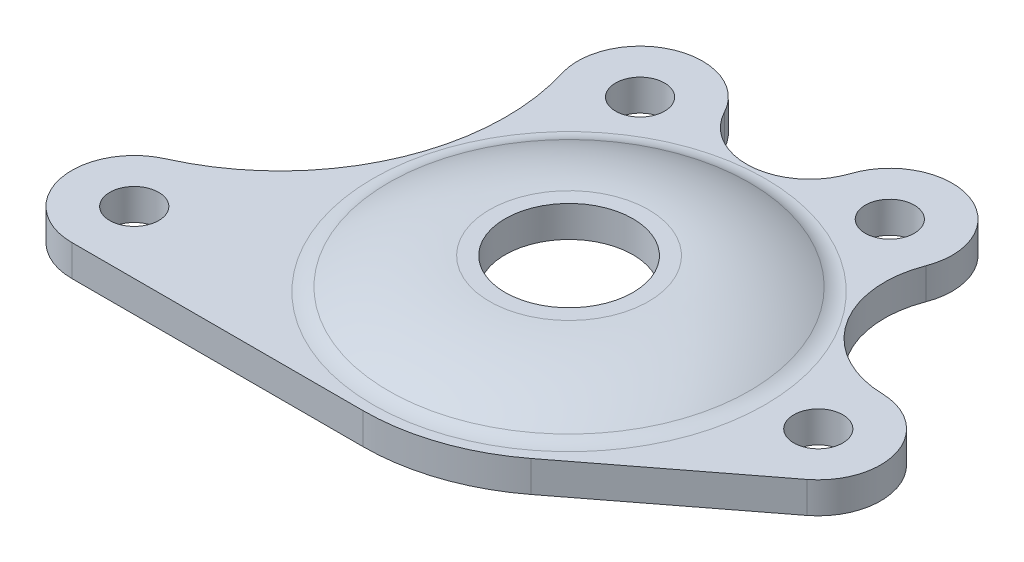
SolidWorks part; units mm, degrees
material "Alum Plate"
ref_plane "Front Plane" through (0, 0, 0) normal (0, 0, 1) x (1, 0, 0)
ref_plane "Top Plane" through (0, 0, 0) normal (0, 1, 0) x (1, 0, 0)
ref_plane "Right Plane" through (0, 0, 0) normal (1, 0, 0) x (0, 0, -1)
sketch "Top Layout" plane through (0, 0, 0) normal (0, 1, 0) x (1, 0, 0)
  line L0 (-114.046, -123.825) -> (-104.775, -123.825) construction
  line L1 (-104.775, -142.875) -> (-101.6, -142.875)
  line L2 (-104.775, -142.875) -> (-104.775, -104.775)
  line L3 (-104.775, -104.775) -> (-101.6, -104.775)
  line L4 (-101.6, -142.875) -> (-101.6, -104.775)
  line L5 (-104.775, -142.875) -> (-101.6, -104.775) construction
  line L6 (-104.775, -104.775) -> (-101.6, -142.875) construction
  line L7 (-19.05, -105.8164) -> (-101.6, -105.8164)
  line L8 (-19.05, -105.8164) -> (-19.05, -141.8336)
  line L9 (-19.05, -141.8336) -> (-101.6, -141.8336)
  line L10 (-101.6, -105.8164) -> (-101.6, -141.8336)
  line L11 (-19.05, -105.8164) -> (-101.6, -141.8336) construction
  line L12 (-19.05, -141.8336) -> (-101.6, -105.8164) construction
  line L13 (-133.096, -85.725) -> (-114.046, -85.725)
  line L14 (-133.096, -85.725) -> (-133.096, -161.925)
  line L15 (-133.096, -161.925) -> (-114.046, -161.925)
  line L16 (-114.046, -85.725) -> (-114.046, -161.925)
  line L17 (-133.096, -85.725) -> (-114.046, -161.925) construction
  line L18 (-133.096, -161.925) -> (-114.046, -85.725) construction
  line L19 (-104.775, -123.825) -> (0, -123.825) construction
  line L20 (0, -123.825) -> (0, 0) construction
  line L21 (-52.3528, -40.1717) -> (0, 0) construction
  line L22 (-70.6449, -16.3328) -> (-18.2922, 23.8388)
  line L23 (-34.0606, -64.0105) -> (18.2922, -23.8388)
  line L24 (-30.9251, 40.3023) -> (-122.2248, -29.7544)
  line L25 (-153.9748, -53.975) -> (-153.9748, -123.825)
  line L26 (-109.5248, -162.052) -> (109.5248, -162.052)
  line L27 (0, -162.052) -> (0, -123.825) construction
  line L28 (-109.5248, -162.052) -> (-109.5248, -20.0093) construction
  line L29 (-104.775, -142.875) -> (-104.775, -152.527)
  line L30 (-104.775, -152.527) -> (104.775, -152.527)
  line L31 (104.775, -104.775) -> (101.6, -104.775)
  line L32 (-144.4498, -73.025) -> (-109.5248, -73.025)
  line L33 (-144.4498, -73.025) -> (-144.4498, -123.825)
  line L34 (-144.4498, -123.825) -> (-109.5248, -123.825) construction
  line L35 (-109.5248, -73.025) -> (-109.5248, -162.052)
  line L36 (-144.4498, -73.025) -> (-109.5248, -123.825) construction
  line L37 (-144.4498, -123.825) -> (-109.5248, -73.025) construction
  line L38 (101.6, -142.875) -> (101.6, -104.775)
  line L39 (104.775, -142.875) -> (101.6, -142.875)
  line L40 (104.775, -142.875) -> (104.775, -104.775)
  line L41 (104.775, -142.875) -> (104.775, -152.527)
  line L42 (109.5248, -162.052) -> (109.5248, -20.0093) construction
  line L43 (30.9251, 40.3023) -> (122.2248, -29.7544)
  line L45 (19.05, -141.8336) -> (101.6, -141.8336)
  line L46 (101.6, -105.8164) -> (101.6, -141.8336)
  line L47 (19.05, -105.8164) -> (101.6, -105.8164)
  line L48 (19.05, -105.8164) -> (19.05, -141.8336)
  line L49 (133.096, -161.925) -> (114.046, -161.925)
  line L50 (114.046, -85.725) -> (114.046, -161.925)
  line L51 (133.096, -85.725) -> (114.046, -85.725)
  line L52 (133.096, -85.725) -> (133.096, -161.925)
  line L53 (144.4498, -123.825) -> (109.5248, -123.825) construction
  line L54 (109.5248, -73.025) -> (109.5248, -162.052)
  line L55 (144.4498, -73.025) -> (109.5248, -73.025)
  line L56 (144.4498, -73.025) -> (144.4498, -123.825)
  line L57 (-109.5248, -123.825) -> (-109.5248, -162.052) construction
  line L62 (-153.9748, -53.975) -> (-122.2248, -53.975)
  line L63 (-122.2248, -53.975) -> (-122.2248, -29.7544)
  line L64 (-144.4498, -123.825) -> (-153.9748, -123.825)
  line L65 (153.9748, -53.975) -> (153.9748, -123.825)
  line L66 (109.5248, -123.825) -> (109.5248, -162.052) construction
  line L67 (144.4498, -123.825) -> (153.9748, -123.825)
  line L68 (122.2248, -29.7544) -> (122.2248, -53.975)
  line L73 (-104.775, -104.775) -> (-104.775, -16.3647) construction
  line L74 (-95.25, -162.052) -> (-95.25, -9.0559) construction
  line L75 (-109.5248, -162.052) -> (-109.5248, -123.825) construction
  line L76 (109.5248, -162.052) -> (109.5248, -123.825) construction
  line L77 (122.2248, -53.975) -> (153.9748, -53.975)
  line L83 (104.775, -155.5496) -> (-104.775, -155.5496) construction
  line L88 (95.25, -162.052) -> (95.25, -9.0559) construction
  line L89 (104.775, -104.775) -> (104.775, -16.3647) construction
  line L92 (-104.775, -152.527) -> (-104.775, -162.052) construction
  line L93 (-14.605, -76.327) -> (14.605, -76.327)
  line L94 (-14.605, -76.327) -> (-14.605, -152.527)
  line L95 (-14.605, -152.527) -> (14.605, -152.527)
  line L96 (14.605, -76.327) -> (14.605, -152.527)
  line L97 (-14.605, -76.327) -> (14.605, -152.527) construction
  line L98 (-14.605, -152.527) -> (14.605, -76.327) construction
  line L99 (104.775, -152.527) -> (104.775, -162.052) construction
  line L100 (-19.05, -105.8164) -> (0, -105.8164) construction
  line L107 (0, -105.8164) -> (19.05, -105.8164) construction
  line L108 (104.775, -123.825) -> (114.046, -123.825) construction
  circle A0 centre (0, 0) radius 114.3
  circle A1 centre (0, 0) radius 6.35
  circle A2 centre (-52.3528, -40.1717) radius 17.8
  circle A3 centre (0, 0) radius 30.0482
  circle A4 centre (-52.3528, -40.1717) radius 30.0482
  arc A5 (-30.9251, 40.3023) -> (30.9251, 40.3023) centre (0, 0) cw
  point P2 (-103.1875, -123.825)
  point P7 (-60.325, -123.825)
  point P12 (-123.571, -123.825)
  point P30 (-126.9873, -98.425)
  point P35 (0, -114.427)
  point P53 (0, -152.527)
  dimension "D1" = 35.6
  dimension "D2" = 12.7
  dimension "D3" = 228.6
  dimension "D11" = 60.0964
  dimension "D12" = 50.8
  dimension "D14" = 52.5
  dimension "D4" = 3.175
  dimension "D5" = 19.05
  dimension "D6" = 76.2
  dimension "D7" = 82.55
  dimension "D8" = 38.1
  dimension "D9" = 104.775
  dimension "D10" = 18.0086
  dimension "D13" = 9.525
  dimension "D15" = 4.7498
  dimension "D16" = 9.525
  dimension "D17" = 9.652
  dimension "D18" = 50.8
  dimension "D19" = 12.446
  dimension "D20" = 65.9892
  dimension "D21" = 19.05
  dimension "D22" = 34.925
  dimension "D23" = 123.825
  dimension "D24" = 12.7
  dimension "D25" = 9.525
  dimension "D26" = 29.21
  dimension "D27" = 76.2
  dimension "D28" = 3.0226
sketch "Side Layout" plane through (0, 0, 0) normal (1, 0, 0) x (0, 0, -1)
  line L0 (0, -38.1) -> (0, 33.7344) construction
  line L1 (-114.3, -20.955) -> (114.3, -20.955)
  line L2 (-114.3, -20.955) -> (-114.3, -33.655)
  line L3 (-114.3, -33.655) -> (114.3, -33.655)
  line L4 (114.3, -20.955) -> (114.3, -33.655)
  line L5 (-114.3, -20.955) -> (114.3, -33.655) construction
  line L6 (-114.3, -33.655) -> (114.3, -20.955) construction
  line L7 (-9.525, -32.9406) -> (9.525, -32.9406)
  line L8 (-9.525, -32.9406) -> (-9.525, -38.1)
  line L9 (-9.525, -38.1) -> (9.525, -38.1)
  line L10 (9.525, -32.9406) -> (9.525, -38.1)
  line L11 (-9.525, -32.9406) -> (9.525, -38.1) construction
  line L12 (-9.525, -38.1) -> (9.525, -32.9406) construction
  line L13 (-11.9126, -29.3338) -> (11.9126, -29.3338)
  line L14 (-11.9126, -29.3338) -> (-11.9126, -32.9406)
  line L15 (-11.9126, -32.9406) -> (11.9126, -32.9406)
  line L16 (11.9126, -29.3338) -> (11.9126, -32.9406)
  line L17 (-11.9126, -29.3338) -> (11.9126, -32.9406) construction
  line L18 (-11.9126, -32.9406) -> (11.9126, -29.3338) construction
  line L19 (-6.35, -32.9406) -> (6.35, -32.9406)
  line L20 (-6.35, -32.9406) -> (-6.35, 33.7344)
  line L21 (-6.35, 33.7344) -> (6.35, 33.7344)
  line L22 (6.35, -32.9406) -> (6.35, 33.7344)
  line L23 (-6.35, -32.9406) -> (6.35, 33.7344) construction
  line L24 (-6.35, 33.7344) -> (6.35, -32.9406) construction
  line L25 (-162.052, 0) -> (-123.825, 0) construction
  line L26 (114.3, -33.655) -> (114.3, 0) construction
  line L27 (-142.875, 19.05) -> (-104.775, 19.05)
  line L28 (-40.1717, -9.525) -> (-40.1717, 5.4) construction
  line L29 (-142.875, 19.05) -> (-142.875, -19.05)
  line L30 (-142.875, -19.05) -> (-104.775, -19.05)
  line L31 (-104.775, 19.05) -> (-104.775, -19.05)
  line L32 (-142.875, 19.05) -> (-104.775, -19.05) construction
  line L33 (-142.875, -19.05) -> (-104.775, 19.05) construction
  line L34 (-130.175, -38.1) -> (-117.9516, -38.1) construction
  line L35 (-57.9717, -14.6) -> (-22.3717, -14.6)
  line L36 (-30.0482, -2.794) -> (30.0482, -2.794)
  line L37 (-30.0482, -2.794) -> (-30.0482, -20.955)
  line L38 (-30.0482, -20.955) -> (30.0482, -20.955)
  line L39 (30.0482, -2.794) -> (30.0482, -20.955)
  line L40 (-30.0482, -2.794) -> (30.0482, -20.955) construction
  line L41 (-30.0482, -20.955) -> (30.0482, -2.794) construction
  line L42 (-30.0482, -2.794) -> (-30.0482, 0) construction
  line L43 (-123.825, 0) -> (0, 0) construction
  line L44 (-57.9717, -14.6) -> (-57.9717, 25.4)
  line L45 (-57.9717, 25.4) -> (-22.3717, 25.4)
  line L46 (-22.3717, -14.6) -> (-22.3717, 25.4)
  line L47 (-19.05, 0) -> (19.05, 0)
  line L48 (-19.05, 0) -> (-19.05, -1.9812)
  line L49 (-19.05, -1.9812) -> (19.05, -1.9812)
  line L50 (19.05, 0) -> (19.05, -1.9812)
  line L51 (-19.05, 0) -> (19.05, -1.9812) construction
  line L52 (-19.05, -1.9812) -> (19.05, 0) construction
  line L53 (-70.2199, -3.175) -> (-10.1235, -3.175)
  line L54 (-70.2199, -3.175) -> (-70.2199, -15.875)
  line L55 (-70.2199, -15.875) -> (-10.1235, -15.875)
  line L56 (-10.1235, -3.175) -> (-10.1235, -15.875)
  line L57 (-70.2199, -3.175) -> (-10.1235, -15.875) construction
  line L58 (-70.2199, -15.875) -> (-10.1235, -3.175) construction
  line L59 (-40.1717, -9.525) -> (-40.1717, 0) construction
  line L60 (-57.9717, -14.6) -> (-22.3717, 25.4) construction
  line L61 (-57.9717, 25.4) -> (-22.3717, -14.6) construction
  line L62 (-22.3717, 0) -> (-57.9717, 0) construction
  line L63 (-137.8162, 0) -> (-123.825, -13.9912) construction
  line L64 (-139.065, 15.24) -> (-108.585, 15.24) construction
  line L65 (-139.065, 15.24) -> (-139.065, -15.24) construction
  line L66 (-139.065, -15.24) -> (-108.585, -15.24) construction
  line L67 (-108.585, 15.24) -> (-108.585, -15.24) construction
  line L68 (-139.065, 15.24) -> (-108.585, -15.24) construction
  line L69 (-139.065, -15.24) -> (-108.585, 15.24) construction
  line L70 (-137.8162, 0) -> (-123.825, 13.9912) construction
  line L71 (-123.825, -13.9912) -> (-109.8338, 0) construction
  line L72 (-123.825, 13.9912) -> (-109.8338, 0) construction
  line L73 (-137.8162, 0) -> (-109.8338, 0) construction
  line L74 (-123.825, -13.9912) -> (-123.825, 13.9912) construction
  line L75 (-6.35, 17.8594) -> (6.35, 17.8594)
  line L76 (114.3, 0) -> (-114.3, 0) construction
  line L77 (-22.3717, 19.05) -> (-6.35, 19.05) construction
  line L78 (-123.825, 38.1) -> (-97.9206, 38.1) construction
  line L79 (-19.05, -3.5814) -> (19.05, -3.5814)
  line L80 (-19.05, -3.5814) -> (-19.05, -1.9812)
  line L81 (-19.05, -1.9812) -> (19.05, -1.9812)
  line L82 (19.05, -3.5814) -> (19.05, -1.9812)
  line L83 (-19.05, -3.5814) -> (19.05, -1.9812) construction
  line L84 (-19.05, -1.9812) -> (19.05, -3.5814) construction
  line L85 (-8.7376, -16.7608) -> (8.7376, -16.7608)
  line L86 (-8.7376, -16.7608) -> (-8.7376, -29.3338)
  line L87 (-8.7376, -29.3338) -> (8.7376, -29.3338)
  line L88 (8.7376, -16.7608) -> (8.7376, -29.3338)
  line L89 (-8.7376, -16.7608) -> (8.7376, -29.3338) construction
  line L90 (-8.7376, -29.3338) -> (8.7376, -16.7608) construction
  line L91 (-8.7376, -3.5814) -> (8.7376, -3.5814)
  line L92 (-8.7376, -3.5814) -> (-8.7376, -16.1544)
  line L93 (-8.7376, -16.1544) -> (8.7376, -16.1544)
  line L94 (8.7376, -3.5814) -> (8.7376, -16.1544)
  line L95 (-8.7376, -3.5814) -> (8.7376, -16.1544) construction
  line L96 (-8.7376, -16.1544) -> (8.7376, -3.5814) construction
  circle A0 centre (-123.825, 0) radius 18.0086
  circle A1 centre (-123.825, 0) radius 38.1
  circle A2 centre (-139.065, 15.24) radius 1.905
  circle A3 centre (-108.585, 15.24) radius 1.905
  circle A4 centre (-108.585, -15.24) radius 1.905
  circle A5 centre (-139.065, -15.24) radius 1.905
  circle A6 centre (-137.8162, 0) radius 1.6002
  circle A7 centre (-123.825, 13.9912) radius 1.6002
  circle A8 centre (-109.8338, 0) radius 1.6002
  circle A9 centre (-123.825, -13.9912) radius 1.6002
  point P0 (0, -27.305)
  point P6 (0, -31.1372)
  point P7 (0, -35.5203)
  point P21 (0, 0.3969)
  point P32 (0, -11.8745)
  point P43 (0, -0.9906)
  point P55 (-40.1717, -9.525)
  point P72 (-40.1717, 5.4)
  point P88 (0, -23.0473)
  point P93 (0, -2.7813)
  point P102 (0, -9.8679)
  dimension "D17" = 3.81
  dimension "D18" = 3.2004
  dimension "D1" = 12.7
  dimension "D2" = 5.1594
  dimension "D3" = 19.05
  dimension "D4" = 3.6068
  dimension "D5" = 23.8252
  dimension "D6" = 12.7
  dimension "D7" = 18.161
  dimension "D8" = 1.9812
  dimension "D9" = 12.7
  dimension "D10" = 40
  dimension "D11" = 25.4
  dimension "D12" = 50.8
  dimension "D13" = 41.275
  dimension "D14" = 30.48
  dimension "D15" = 4.445
  dimension "D16" = 19.7866
  dimension "D19" = 15.875
  dimension "D20" = 6.35
  dimension "D21" = 38.1
  dimension "D22" = 1.6002
  dimension "D23" = 38.1
  dimension "D24" = 17.4752
  dimension "D25" = 12.573
ref_plane "Plane1" through (0, 25.4, 0) normal (0, 1, 0) x (1, 0, 0)
sketch "Sketch3" plane through (0, 25.4, 0) normal (0, 1, 0) x (1, 0, 0)
  line L0 (-104.775, -36.3747) -> (-30.9251, 20.2924)
  line L1 (-104.775, -104.775) -> (-104.775, -16.3647) construction
  line L2 (0, -200130.175) -> (0, 199882.0484) construction
  line L3 (-30.9251, 40.3023) -> (-122.2248, -29.7544) construction
  line L5 (-104.775, -36.3747) -> (-104.775, -77.6497)
  line L6 (-92.075, -77.6497) -> (-104.775, -77.6497)
  line L7 (30.9251, 20.2924) -> (104.775, -36.3747)
  line L8 (104.775, -77.6497) -> (92.075, -77.6497)
  line L9 (104.775, -36.3747) -> (104.775, -77.6497)
  line L11 (104.775, -104.775) -> (104.775, -16.3647) construction
  line L12 (30.9251, 40.3023) -> (122.2248, -29.7544) construction
  line L13 (92.075, -74.6536) -> (24.1423, -22.5271)
  line L14 (-32.2514, -66.3682) -> (20.1013, -26.1965)
  line L15 (-30.9251, 20.2924) -> (0, 44.022)
  line L16 (0, 44.022) -> (30.9251, 20.2924)
  line L17 (-92.075, -77.6497) -> (-92.075, -73.1917)
  line L19 (-92.075, -73.1917) -> (-52.3528, -73.1917)
  line L20 (92.075, -74.6536) -> (92.075, -77.6497)
  circle A0 centre (-52.3528, -40.1717) radius 17.8 construction
  circle A1 centre (-52.3528, -40.1717) radius 17.8
  circle A2 centre (0, 0) radius 6.35
  circle A3 centre (0, 0) radius 6.35 construction
  arc A4 (-52.3528, -73.1917) -> (-32.2514, -66.3682) centre (-52.3528, -40.1717) ccw
  arc A5 (20.1013, -26.1965) -> (24.1423, -22.5271) centre (0, 0) ccw
  arc A6 (30.9251, 20.2924) -> (-30.9251, 20.2924) centre (0, -20.01) ccw construction
  point P28 (0, 44.022)
  dimension "D1" = 33.02
  dimension "D5" = 50.8
  dimension "D2" = 41.275
  dimension "D3" = 34.925
  dimension "D4" = 12.7
  dimension "D6" = 38.1
extrude "Boss-Extrude1" [suppressed] add sketch "Sketch3" against normal blind 6.35
ref_plane "Plane3" through (-104.775, 0, 0) normal (-1, 0, 0) x (0, 0, 1)
sketch "Sketch6" plane through (-104.775, 0, 0) normal (-1, 0, 0) x (0, 0, 1)
  line L0 (162.052, -25.4) -> (162.052, 25.4)
  line L1 (162.052, 25.4) -> (77.6497, 25.4)
  line L2 (36.3747, 25.4) -> (77.6497, 25.4) construction
  line L3 (147.7645, 11.1125) -> (162.052, 11.1125) construction
  line L4 (162.052, 0) -> (71.2997, 0) construction
  line L5 (77.6497, 25.4) -> (77.6497, 19.05)
  line L6 (77.6497, 19.05) -> (36.3747, 19.05)
  line L7 (36.3747, 19.05) -> (36.3747, 6.35)
  line L8 (36.3747, 6.35) -> (71.2997, 6.35)
  line L10 (99.6315, -3.175) -> (99.6315, 11.1125) construction
  line L11 (71.2997, -25.4) -> (162.052, -25.4)
  line L13 (71.2997, 6.35) -> (71.2997, -25.4)
  line L14 (152.527, -25.4) -> (152.527, 25.4) construction
  line L15 (99.6315, 11.1125) -> (99.6315, 25.4) construction
  line L16 (147.7645, 11.1125) -> (147.7645, 25.4) construction
  line L17 (94.869, -7.9375) -> (104.394, -7.9375) construction
  line L18 (94.869, -7.9375) -> (94.869, 25.4) construction
  line L19 (94.869, 25.4) -> (104.394, 25.4) construction
  line L20 (104.394, -7.9375) -> (104.394, 25.4) construction
  line L21 (94.869, -7.9375) -> (104.394, 25.4) construction
  line L22 (94.869, 25.4) -> (104.394, -7.9375) construction
  line L23 (147.7645, 11.1125) -> (147.7645, -3.175) construction
  line L24 (104.394, -7.9375) -> (123.825, -7.9375) construction
  line L25 (143.002, -7.9375) -> (152.527, -7.9375) construction
  line L26 (143.002, -7.9375) -> (143.002, 25.4) construction
  line L27 (143.002, 25.4) -> (152.527, 25.4) construction
  line L28 (152.527, -7.9375) -> (152.527, 25.4) construction
  line L29 (143.002, -7.9375) -> (152.527, 25.4) construction
  line L30 (143.002, 25.4) -> (152.527, -7.9375) construction
  line L31 (123.825, -7.9375) -> (152.527, -7.9375) construction
  line L32 (104.775, 19.05) -> (104.775, -19.05) construction
  line L34 (155.702, -25.4) -> (155.702, 25.4) construction
  circle A0 centre (109.8338, 0) radius 1.6002 construction
  circle A1 centre (123.825, 13.9912) radius 1.6002 construction
  circle A2 centre (137.8162, 0) radius 1.6002 construction
  circle A3 centre (123.825, -13.9912) radius 1.6002 construction
  circle A4 centre (109.8338, 0) radius 1.6002 construction
  circle A5 centre (123.825, 13.9912) radius 1.6002 construction
  circle A6 centre (137.8162, 0) radius 1.6002 construction
  circle A7 centre (123.825, -13.9912) radius 1.6002 construction
  circle A8 centre (123.825, 0) radius 18.0086 construction
  circle A9 centre (123.825, 0) radius 18.0086 construction
  circle A10 centre (123.825, 0) radius 9.525
  circle A11 centre (108.585, -15.24) radius 1.905 construction
  circle A12 centre (108.585, 15.24) radius 1.905 construction
  circle A13 centre (139.065, 15.24) radius 1.905 construction
  circle A14 centre (139.065, -15.24) radius 1.905 construction
  circle A15 centre (108.585, -15.24) radius 1.905
  circle A16 centre (108.585, 15.24) radius 1.905
  circle A17 centre (139.065, 15.24) radius 1.905
  circle A18 centre (139.065, -15.24) radius 1.905
  circle A19 centre (147.7645, 11.1125) radius 2.5527
  circle A26 centre (99.6315, 11.1125) radius 2.5527
  circle A27 centre (99.6315, -3.175) radius 2.5527
  circle A28 centre (147.7645, -3.175) radius 2.5527
  point P29 (0, 0)
  point P55 (99.6315, 8.7312)
  point P61 (147.7645, 8.7312)
  dimension "D4" = 19.05
  dimension "D7" = 5.1054
  dimension "D1" = 6.35
  dimension "D2" = 12.7
  dimension "D3" = 25.4
  dimension "D5" = 6.35
  dimension "D6" = 3.175
  dimension "D8" = 0.381
  dimension "D9" = 14.2875
  dimension "D10" = 9.525
  dimension "D12" = 33.3375
extrude "Side Plate Extrude" [suppressed] add sketch "Sketch6" along normal up to vertex up to point (-109.5248, 0, 73.025)
ref_plane "Plane4" through (0, 19.05, 0) normal (0, 1, 0) x (1, 0, 0)
sketch "Sketch12" plane through (0, 19.05, 0) normal (0, 1, 0) x (1, 0, 0)
  line L0 (-104.775, -77.6497) -> (-104.775, -36.3747)
  line L1 (-104.775, -36.3747) -> (-92.075, -36.3747)
  line L3 (-92.075, -36.3747) -> (-92.075, -77.6497)
  line L5 (-92.075, -77.6497) -> (-104.775, -77.6497)
  line L6 (-98.425, -77.6497) -> (-98.425, -63.3622) construction
  line L7 (-98.425, -63.3622) -> (-98.425, -50.6622) construction
  line L8 (-98.425, -50.6622) -> (-98.425, -36.3747) construction
  line L10 (-98.425, -36.3747) -> (-104.775, -36.3747) construction
  circle A0 centre (-98.425, -63.3622) radius 2.5527
  circle A1 centre (-98.425, -50.6622) radius 2.5527
  dimension "D2" = 5.1054
  dimension "D1" = 12.7
  dimension "D3" = 12.7
sketch "Sketch24" [suppressed] plane through (0, -12.7, 0) normal (0, -1, 0) x (1, 0, 0)
  line L5 (-104.775, 94.8709) -> (-104.775, 152.527)
  line L7 (-104.775, 152.527) -> (104.775, 152.527)
  line L9 (104.775, 152.527) -> (104.775, 94.8709)
  line L10 (-99.695, 92.4539) -> (-99.695, 94.8709)
  line L12 (-104.775, 94.8709) -> (-104.775, 77.6497)
  line L28 (104.775, 77.6497) -> (104.775, 94.8709)
  line L45 (104.775, 77.6497) -> (104.775, 94.8709)
  line L47 (-104.775, 94.8709) -> (-104.775, 77.6497)
  line L48 (-104.775, 77.6497) -> (-92.075, 77.6497)
  line L49 (-104.775, 77.6497) -> (-92.075, 77.6497)
  line L51 (89.9708, 82.7297) -> (86.995, 82.7297)
  line L52 (92.075, 77.6497) -> (104.775, 77.6497)
  line L53 (92.075, 77.6497) -> (104.775, 77.6497)
  line L54 (99.695, 94.8709) -> (99.695, 92.4539)
  line L56 (28.6663, 26.0276) -> (-29.1589, 70.3984)
  line L57 (-86.995, 82.7297) -> (-89.9708, 82.7297)
  line L58 (19.9724, 26.2955) -> (20.1013, 26.1965)
  line L59 (19.9724, 26.2955) -> (20.1013, 26.1965)
  line L60 (-99.695, 94.8709) -> (-104.775, 94.8709)
  line L61 (104.775, 94.8709) -> (99.695, 94.8709)
  line L74 (86.995, 82.7297) -> (86.995, 77.1588)
  line L76 (86.995, 77.1588) -> (31.7579, 34.7739)
  line L78 (-52.3528, 78.2717) -> (-86.995, 78.2717)
  line L79 (-32.2514, 66.3682) -> (19.7754, 26.4466)
  line L80 (-86.995, 78.2717) -> (-86.995, 82.7297)
  line L82 (-92.075, 77.6497) -> (-92.075, 73.1917)
  line L83 (-92.075, 77.6497) -> (-92.075, 73.1917)
  line L84 (-92.075, 73.1917) -> (-52.3528, 73.1917)
  line L85 (-92.075, 73.1917) -> (-52.3528, 73.1917)
  line L86 (24.1423, 22.5271) -> (92.075, 74.6536)
  line L87 (24.1423, 22.5271) -> (92.075, 74.6536)
  line L88 (92.075, 74.6536) -> (92.075, 77.6497)
  line L89 (92.075, 74.6536) -> (92.075, 77.6497)
  line L90 (-32.2514, 66.3682) -> (19.7754, 26.4466)
  line L91 (19.7754, 26.4466) -> (19.9724, 26.2955)
  line L92 (19.7754, 26.4466) -> (19.9724, 26.2955)
  circle A0 centre (-97.155, 85.2697) radius 4.826 construction
  circle A1 centre (-97.155, 85.2697) radius 2.4892
  circle A6 centre (97.155, 85.2697) radius 2.4892
  circle A7 centre (24.5121, 32.4156) radius 2.4892
  arc A9 (99.695, 92.4539) -> (89.9708, 82.7297) centre (97.155, 85.2697) ccw
  circle A11 centre (24.5121, 32.4156) radius 4.826 construction
  arc A17 (-89.9708, 82.7297) -> (-99.695, 92.4539) centre (-97.155, 85.2697) ccw
  arc A18 (-29.1589, 70.3984) -> (-52.3528, 78.2717) centre (-52.3528, 40.1717) ccw
  arc A19 (31.7579, 34.7739) -> (28.6663, 26.0276) centre (24.5121, 32.4156) ccw
  arc A20 (-32.2514, 66.3682) -> (-52.3528, 73.1917) centre (-52.3528, 40.1717) ccw
  arc A21 (24.1423, 22.5271) -> (20.1013, 26.1965) centre (0, 0) ccw
  arc A22 (24.1423, 22.5271) -> (20.1013, 26.1965) centre (0, 0) ccw
  arc A30 (-32.2514, 66.3682) -> (-52.3528, 73.1917) centre (-52.3528, 40.1717) ccw
  dimension "D3" = 4.9784
  dimension "D1" = 0
sketch "Sketch38" [suppressed] plane through (-104.775, 0, 0) normal (-1, 0, 0) x (0, 0, 1)
  line L1 (152.527, -7.9375) -> (143.002, -7.9375)
  line L2 (152.527, -7.9375) -> (152.527, 25.4)
  line L3 (152.527, 25.4) -> (143.002, 25.4)
  line L4 (143.002, -7.9375) -> (143.002, 25.4)
  line L5 (152.527, -7.9375) -> (143.002, 25.4) construction
  line L6 (152.527, 25.4) -> (143.002, -7.9375) construction
  point P4 (147.7645, 8.7312)
extrude "Cut-Extrude16" [suppressed] cut sketch "Sketch38" against normal blind 9.525
sketch "Sketch46" [suppressed] plane through (-104.775, 0, 0) normal (-1, 0, 0) x (0, 0, 1)
  line L0 (142.875, 19.05) -> (104.775, -19.05) construction
  line L1 (104.14, 19.685) -> (143.51, 19.685)
  line L2 (104.14, 19.685) -> (104.14, -19.685)
  line L3 (104.14, -19.685) -> (143.51, -19.685)
  line L4 (143.51, 19.685) -> (143.51, -19.685)
  line L5 (104.14, 19.685) -> (143.51, -19.685) construction
  line L6 (104.14, -19.685) -> (143.51, 19.685) construction
  point P0 (123.825, 0)
  dimension "D1" = 39.37
extrude "Cut-Extrude21" [suppressed] cut sketch "Sketch46" against normal blind 6.985
ref_plane "Plane5" through (0, 0, 152.527) normal (0, 0, 1) x (1, 0, 0)
sketch "Sketch41" plane through (0, 0, 152.527) normal (0, 0, 1) x (1, 0, 0)
  line L0 (-104.775, -7.9375) -> (-104.775, 25.4) construction
  line L1 (-104.775, -7.9375) -> (-104.775, 12.7)
  line L2 (-104.775, -7.9375) -> (104.775, -7.9375)
  line L3 (104.775, -7.9375) -> (104.775, 12.7)
  line L4 (104.775, 25.4) -> (-104.775, 25.4)
  line L5 (0, -7.9375) -> (0, 25.4) construction
  line L6 (-104.775, 3.9624) -> (-100.0125, 3.9624) construction
  line L7 (-100.0125, 3.9624) -> (-100.0125, 25.4) construction
  line L8 (104.775, 3.9624) -> (100.0125, 3.9624) construction
  line L9 (100.0125, 3.9624) -> (100.0125, 25.4) construction
  line L10 (19.05, 20.6375) -> (23.8252, 20.6375) construction
  line L11 (19.05, 15.875) -> (78.5876, 15.875) construction
  line L12 (19.05, 15.875) -> (19.05, 25.4) construction
  line L13 (19.05, 25.4) -> (78.5876, 25.4) construction
  line L14 (78.5876, 15.875) -> (78.5876, 25.4) construction
  line L15 (19.05, 15.875) -> (78.5876, 25.4) construction
  line L16 (19.05, 25.4) -> (78.5876, 15.875) construction
  line L17 (23.8252, 20.6375) -> (38.1127, 20.6375) construction
  line L18 (38.1127, 20.6375) -> (52.4002, 20.6375) construction
  line L19 (52.4002, 20.6375) -> (66.6877, 20.6375) construction
  line L20 (-104.775, 25.4) -> (-112.395, 25.4)
  line L21 (-112.395, 25.4) -> (-112.395, 3.175)
  line L22 (-112.395, 3.175) -> (-109.5248, 3.175)
  line L23 (-109.5248, 3.175) -> (-109.5248, 12.7)
  line L24 (-109.5248, 12.7) -> (-104.775, 12.7)
  line L25 (-104.775, 12.7) -> (-104.775, 25.4) construction
  line L26 (104.775, 25.4) -> (112.395, 25.4)
  line L27 (112.395, 25.4) -> (112.395, 3.175)
  line L28 (112.395, 3.175) -> (109.5248, 3.175)
  line L29 (109.5248, 3.175) -> (109.5248, 12.7)
  line L30 (109.5248, 12.7) -> (104.775, 12.7)
  line L31 (104.775, 12.7) -> (104.775, 25.4) construction
  line L32 (-100.0125, 3.9624) -> (-87.3125, 3.9624) construction
  line L33 (-63.5, -1.5875) -> (0, -1.5875) construction
  line L34 (0, -1.5875) -> (63.5, -1.5875) construction
  line L35 (63.5, -1.5875) -> (63.5, -7.9375) construction
  circle A0 centre (-100.0125, 3.9624) radius 2.5527
  circle A1 centre (100.0125, 3.9624) radius 2.5527
  circle A2 centre (23.8252, 20.6375) radius 2.5527
  circle A3 centre (38.1127, 20.6375) radius 2.5527
  circle A4 centre (52.4002, 20.6375) radius 2.5527
  circle A5 centre (66.6877, 20.6375) radius 2.5527
  circle A6 centre (-66.6877, 20.6375) radius 2.5527
  circle A7 centre (-52.4002, 20.6375) radius 2.5527
  circle A8 centre (-38.1127, 20.6375) radius 2.5527
  circle A9 centre (-23.8252, 20.6375) radius 2.5527
  circle A10 centre (-87.3125, 3.9624) radius 2.5527
  circle A11 centre (87.3125, 3.9624) radius 2.5527
  circle A12 centre (-63.5, -1.5875) radius 2.5527
  circle A13 centre (63.5, -1.5875) radius 2.5527
  point P14 (48.8188, 20.6375)
  dimension "D3" = 5.1054
  dimension "D7" = 5.1054
  dimension "D1" = 21.4376
  dimension "D2" = 4.7625
  dimension "D4" = 9.525
  dimension "D5" = 59.5376
  dimension "D6" = 4.7752
  dimension "D8" = 14.2875
  dimension "D9" = 7.62
  dimension "D10" = 4.7498
  dimension "D11" = 12.7
  dimension "D12" = 9.525
  dimension "D13" = 19.05
  dimension "D14" = 12.7
  dimension "D15" = 6.35
  dimension "D16" = 63.5
sketch "Sketch43" [suppressed] plane through (-109.5248, 0, 0) normal (-1, 0, 0) x (0, 0, 1)
  line L1 (152.527, 12.7) -> (155.702, 12.7)
  line L2 (152.527, 12.7) -> (152.527, 25.4)
  line L3 (152.527, 25.4) -> (155.702, 25.4)
  line L4 (155.702, 12.7) -> (155.702, 25.4)
  line L5 (152.527, 12.7) -> (155.702, 25.4) construction
  line L6 (152.527, 25.4) -> (155.702, 12.7) construction
  line L7 (162.052, 25.4) -> (77.6497, 25.4) construction
  point P4 (154.1145, 19.05)
  dimension "D1" = 3.175
sketch "Sketch44" plane through (0, 25.4, 0) normal (0, 1, 0) x (1, 0, 0)
  line L0 (73.8315, -147.7645) -> (73.8315, -152.527) construction
  line L1 (92.075, -74.6536) -> (92.075, -77.6497) construction
  line L2 (-92.075, -77.6497) -> (-92.075, -73.1917) construction
  line L3 (0, -123.825) -> (0, 0) construction
  line L4 (-92.075, -73.1917) -> (-52.3528, -73.1917) construction
  line L5 (-104.775, -104.775) -> (-104.775, -16.3647) construction
  line L6 (-32.2514, -66.3682) -> (20.1013, -26.1965) construction
  line L21 (-104.775, -68.1247) -> (-104.775, -152.527)
  line L22 (-104.775, -152.527) -> (104.775, -152.527)
  line L23 (104.775, -152.527) -> (104.775, -68.1247)
  line L34 (-104.775, -99.6315) -> (-100.0125, -99.6315) construction
  line L35 (-104.775, -147.7645) -> (-100.0125, -147.7645) construction
  line L36 (0, -152.527) -> (0, -35.6178) construction
  line L38 (30.969, -147.7645) -> (45.2565, -147.7645) construction
  line L39 (45.2565, -147.7645) -> (59.544, -147.7645) construction
  line L40 (59.544, -147.7645) -> (73.8315, -147.7645) construction
  line L41 (23.8252, -152.527) -> (30.969, -152.527) construction
  line L42 (104.775, -152.527) -> (-104.775, -152.527) construction
  line L43 (30.969, -152.527) -> (38.1127, -152.527) construction
  line L44 (30.969, -152.527) -> (30.969, -147.7645) construction
  line L45 (-92.075, -77.6497) -> (-104.775, -77.6497) construction
  line L48 (-35.1507, -62.5899) -> (-8.9743, -42.504) construction
  line L49 (-8.9743, -42.504) -> (17.2021, -22.4182) construction
  line L50 (45.5313, -32.9364) -> (87.3125, -64.9962) construction
  line L51 (92.075, -74.6536) -> (24.1423, -22.5271) construction
  line L52 (104.775, -77.6497) -> (92.075, -77.6497) construction
  line L79 (-104.775, -68.1247) -> (-92.075, -68.1247)
  line L80 (-92.075, -68.1247) -> (-92.075, -63.6667)
  line L85 (21.8118, -8.7328) -> (92.075, -62.6476)
  line L86 (-38.0499, -58.8115) -> (14.3028, -18.6398)
  line L87 (-92.075, -63.6667) -> (-52.3528, -63.6667)
  line L88 (92.075, -62.6476) -> (92.075, -68.1247)
  line L89 (92.075, -68.1247) -> (104.775, -68.1247)
  circle A0 centre (-73.8315, -147.7645) radius 2.5527
  circle A1 centre (-59.544, -147.7645) radius 2.5527
  circle A2 centre (-45.2565, -147.7645) radius 2.5527
  circle A3 centre (-30.969, -147.7645) radius 2.5527
  circle A17 centre (-100.0125, -99.6315) radius 2.5527
  circle A18 centre (-100.0125, -147.7645) radius 2.5527
  circle A19 centre (100.0125, -147.7645) radius 2.5527
  circle A20 centre (100.0125, -99.6315) radius 2.5527
  circle A21 centre (30.969, -147.7645) radius 2.5527
  circle A22 centre (45.2565, -147.7645) radius 2.5527
  circle A23 centre (59.544, -147.7645) radius 2.5527
  circle A24 centre (73.8315, -147.7645) radius 2.5527
  circle A25 centre (-87.3125, -68.4292) radius 4.7625 construction
  circle A26 centre (-35.1507, -62.5899) radius 4.7625 construction
  circle A27 centre (-8.9743, -42.504) radius 4.7625 construction
  circle A28 centre (17.2021, -22.4182) radius 4.7625 construction
  circle A29 centre (45.5313, -32.9364) radius 4.7625 construction
  circle A30 centre (87.3125, -64.9962) radius 4.7625 construction
  circle A32 centre (-87.3125, -68.4292) radius 2.5527
  circle A33 centre (-35.1507, -62.5899) radius 2.5527
  circle A34 centre (-8.9743, -42.504) radius 2.5527 construction
  circle A35 centre (17.2021, -22.4182) radius 2.5527
  circle A36 centre (45.5313, -32.9364) radius 2.5527
  circle A37 centre (87.3125, -64.9962) radius 2.5527
  circle A38 centre (-97.155, -85.2697) radius 7.62 construction
  circle A39 centre (97.155, -85.2697) radius 7.62 construction
  circle A40 centre (24.5121, -32.4156) radius 7.62 construction
  arc A41 (20.1013, -26.1965) -> (24.1423, -22.5271) centre (0, 0) ccw construction
  circle A42 centre (-97.155, -85.2697) radius 2.5527
  circle A43 centre (24.5121, -32.4156) radius 2.5527
  circle A44 centre (97.155, -85.2697) radius 2.5527
  arc A56 (14.3028, -18.6398) -> (21.8118, -8.7328) centre (0, 0) ccw
  arc A57 (-52.3528, -63.6667) -> (-38.0499, -58.8115) centre (-52.3528, -40.1717) ccw
  point P4 (-104.775, -152.527)
  dimension "D2" = 5.1054
  dimension "D7" = 5.1054
  dimension "D8" = 15.24
  dimension "D3" = 9.525
  dimension "D9" = 9.525
  dimension "D4" = 4.7625
  dimension "D5" = 14.2875
  dimension "D6" = 9.525
  dimension "D1" = 4.7625
  dimension "D10" = 52.664
sketch "Sketch82" [suppressed] plane through (0, 28.829, 0) normal (0, 1, 0) x (1, 0, 0)
  line L0 (-52.3528, -63.6667) -> (-92.075, -63.6667) construction
  line L1 (-52.3528, -65.5717) -> (-52.3528, -63.6667) construction
  line L2 (-12.4467, -41.5667) -> (-13.6064, -40.0553) construction
  line L3 (14.3028, -18.6398) -> (-38.0499, -58.8115) construction
  line L4 (24.5175, -13.2101) -> (25.6772, -11.6988) construction
  line L5 (92.075, -62.6476) -> (21.8118, -8.7328) construction
  line L6 (58.2962, -39.1295) -> (59.4559, -37.6181) construction
  line L7 (21.4643, -9.5551) -> (21.8118, -8.7328)
  line L8 (21.8118, -8.7328) -> (22.2143, -9.0416)
  circle A0 centre (-52.3528, -65.5717) radius 4.7625
  circle A1 centre (-12.4467, -41.5667) radius 4.7625
  arc A2 (21.4643, -9.5551) -> (22.2143, -9.0416) centre (24.5175, -13.2101) ccw
  circle A3 centre (58.2962, -39.1295) radius 4.7625
  arc A4 (14.3028, -18.6398) -> (21.8118, -8.7328) centre (0, 0) ccw construction
  dimension "D1" = 9.525
  dimension "D2" = 1.905
  dimension "D3" = 30.8104
  dimension "D4" = 83.6926
  dimension "D5" = 41.1154
extrude "Cut-Extrude38" [suppressed] cut sketch "Sketch82" against normal up to surface (3.429 mm away)
sketch "Sketch45" [suppressed] plane through (0, -25.4, 0) normal (0, -1, 0) x (1, 0, 0)
  circle A2 centre (24.5121, 32.4156) radius 6.35
  circle A4 centre (-97.155, 85.2697) radius 6.35
  circle A5 centre (97.155, 85.2697) radius 6.35
  dimension "D1" = 12.7
ref_plane "Plane6" through (0, 19.05, 0) normal (0, 1, 0) x (1, 0, 0)
sketch "Sketch59" plane through (0, 19.05, 0) normal (0, 1, 0) x (1, 0, 0)
  line L0 (0, 22.408) -> (0, 30.79) construction
  line L1 (-19.1436, 18.7673) -> (-24.2463, 25.4172) construction
  line L2 (0, 33.4567) -> (-5.1026, 40.1066) construction
  line L3 (-5.1026, 40.1066) -> (-24.2463, 25.4172) construction
  line L4 (-104.775, -36.3747) -> (-30.9251, 20.2924) construction
  line L5 (-19.1436, 18.7673) -> (0, 33.4567) construction
  circle A0 centre (0, 22.408) radius 4.7625
  circle A2 centre (-19.1436, 18.7673) radius 4.7625
  arc A3 (30.9251, 20.2924) -> (-30.9251, 20.2924) centre (0, -20.01) ccw construction
  dimension "D3" = 9.525
  dimension "D1" = 8.382
  dimension "D2" = 24.13
sketch "Sketch47" plane through (0, 25.4, 0) normal (0, 1, 0) x (1, 0, 0)
  line L0 (-21.3485, -42.7945) -> (-23.7291, -44.6212) construction
  line L1 (-81.9672, -61.1267) -> (-75.3534, -61.1267) construction
  line L2 (-19.1436, 18.7673) -> (-38.2872, 4.0779) construction
  line L3 (-38.2872, 4.0779) -> (-57.4308, -10.6115) construction
  line L4 (-57.4308, -10.6115) -> (-76.5745, -25.3009) construction
  line L5 (-19.1436, 18.7673) -> (0, 33.4567) construction
  line L6 (-76.5745, -25.3009) -> (-65.8758, -19.4248) construction
  line L7 (-65.8758, -19.4248) -> (-57.4308, -10.6115) construction
  line L9 (-87.7466, -52.146) -> (-71.6552, -16.7941)
  line L10 (-38.0499, -58.8115) -> (14.3028, -18.6398) construction
  line L11 (-81.9672, -54.7767) -> (-52.3528, -40.1717) construction
  line L12 (-52.3528, -40.1717) -> (-65.8758, -19.4248) construction
  line L13 (-92.075, -63.6667) -> (-52.3528, -63.6667) construction
  line L14 (-70.5066, -49.3452) -> (-83.977, -62.8156) construction
  line L15 (-23.7291, -44.6212) -> (-39.5962, -56.7964)
  line L16 (-52.3528, -61.1267) -> (-81.9672, -61.1267)
  line L17 (-42.4227, -17.4847) -> (-52.3528, -40.1717) construction
  line L18 (-52.3528, -40.1717) -> (-27.5947, -39.5834) construction
  line L19 (-81.9672, -54.7767) -> (-65.8758, -19.4248) construction
  line L20 (-65.8758, -19.4248) -> (-42.4227, -17.4847) construction
  line L21 (-42.4227, -17.4847) -> (-27.5947, -39.5834) construction
  line L22 (-83.977, -62.8156) -> (-74.9967, -71.7959) construction
  line L23 (-74.9967, -71.7959) -> (-61.5263, -58.3255) construction
  line L24 (-79.4868, -67.3058) -> (-52.3528, -40.1717) construction
  line L25 (-52.3528, -60.5117) -> (-52.3528, -40.1717) construction
  arc A0 (-87.7466, -52.146) -> (-81.9672, -61.1267) centre (-81.9672, -54.7767) ccw
  arc A1 (-23.7291, -44.6212) -> (-27.4458, -33.2351) centre (-27.5947, -39.5834) ccw
  arc A2 (-60.2505, -16.4788) -> (-71.6552, -16.7941) centre (-65.8758, -19.4248) ccw
  arc A3 (-36.4919, -19.7535) -> (-48.4556, -15.5031) centre (-42.4227, -17.4847) ccw
  arc A4 (-21.3485, -42.7945) -> (-75.3534, -61.1267) centre (-52.3528, -40.1717) ccw construction
  arc A5 (-52.3528, -63.6667) -> (-38.0499, -58.8115) centre (-52.3528, -40.1717) ccw construction
  arc A6 (-52.3528, -61.1267) -> (-39.5962, -56.7964) centre (-52.3528, -40.1717) ccw
  circle A7 centre (-81.9672, -54.7767) radius 2.4892
  circle A8 centre (-65.8758, -19.4248) radius 2.4892
  circle A9 centre (-42.4227, -17.4847) radius 2.4892
  circle A10 centre (-27.5947, -39.5834) radius 2.4892
  circle A11 centre (-52.3528, -40.1717) radius 6.5
  arc A13 (-60.2505, -16.4788) -> (-48.4556, -15.5031) centre (-54.5593, -13.4984) ccw
  arc A14 (-36.4919, -19.7535) -> (-27.4458, -33.2351) centre (-27.2129, -23.3031) ccw
  circle A15 centre (-52.3528, -40.1717) radius 20.34 construction
  circle A16 centre (-52.3528, -40.1717) radius 17.8 construction
  dimension "D2" = 62.23
  dimension "D3" = 4.9784
  dimension "D7" = 13
  dimension "D8" = 45
  dimension "D10" = 12.7
  dimension "D11" = 2.54
  dimension "D4" = 2.54
  dimension "D5" = 33.02
  dimension "D6" = 6.35
  dimension "D9" = 65
  dimension "D12" = 19.05
extrude "Motor Mount Extrude-------" add sketch "Sketch47" along normal blind 6.35
sketch "Sketch48" plane through (0, 31.75, 0) normal (0, 1, 0) x (1, 0, 0)
  line L0 (-52.3528, -40.1717) -> (-52.3528, -27.6717) construction
  circle A0 centre (-52.3528, -27.6717) radius 1.5
  dimension "D1" = 3
  dimension "D2" = 12.5
extrude "Cut-Extrude22" [suppressed] cut sketch "Sketch48" against normal through all
ref_axis "Axis1" through (-52.3528, 31.75, 40.1717) along (0, -1, 0)
pattern_circular "CirPattern1" [suppressed] count 4 over 360 about axis through (-52.3528, 31.75, 40.1717) along (0, -1, 0) of bodies 167
sketch "Sketch85" plane through (0, 31.75, 0) normal (0, 1, 0) x (1, 0, 0)
  line L0 (-71.6552, -16.7941) -> (-87.7466, -52.146)
  arc A0 (-84.5565, -48.9786) -> (-71.9487, -21.28) centre (-93.9279, -27.9943) ccw
  circle A1 centre (-52.3528, -40.1717) radius 20.34 construction
  arc A2 (-60.2505, -16.4788) -> (-48.4556, -15.5031) centre (-54.5593, -13.4984) ccw construction
  arc A3 (-87.7466, -52.146) -> (-84.5565, -48.9786) centre (-81.9672, -54.7767) cw
  arc A4 (-71.6552, -16.7941) -> (-71.9487, -21.28) centre (-65.8758, -19.4248) ccw
extrude "Cut-Extrude41" cut sketch "Sketch85" against normal through all
sketch "Sketch124" [suppressed] plane through (0, 31.75, 0) normal (0, 1, 0) x (1, 0, 0)
  line L5 (-81.3322, -63.2534) -> (-81.3322, -63.5397)
  line L6 (-81.3322, -63.5397) -> (-59.1072, -63.5397)
  line L7 (-59.1072, -63.5397) -> (-59.1072, -63.4127)
  line L8 (-56.8212, -61.1267) -> (-52.3528, -61.1267)
  line L9 (-39.5962, -56.7964) -> (-23.7291, -44.6212)
  line L10 (-81.3322, -63.2534) -> (-81.3322, -63.5397)
  line L11 (-81.3322, -63.5397) -> (-59.1072, -63.5397)
  line L12 (-59.1072, -63.5397) -> (-59.1072, -63.4127)
  line L13 (-56.8212, -61.1267) -> (-52.3528, -61.1267)
  line L14 (-39.5962, -56.7964) -> (-23.7291, -44.6212)
  circle A1 centre (-39.8528, -40.1717) radius 1.5
  circle A2 centre (-39.8528, -40.1717) radius 1.5
  circle A3 centre (-52.3528, -52.6717) radius 1.5
  circle A4 centre (-52.3528, -52.6717) radius 1.5
  circle A5 centre (-64.8528, -40.1717) radius 1.5
  circle A6 centre (-64.8528, -40.1717) radius 1.5
  circle A7 centre (-52.3528, -27.6717) radius 1.5
  circle A8 centre (-52.3528, -27.6717) radius 1.5
  circle A9 centre (-27.5947, -39.5834) radius 2.4892
  circle A10 centre (-27.5947, -39.5834) radius 2.4892
  circle A11 centre (-65.8758, -19.4248) radius 2.4892
  circle A12 centre (-65.8758, -19.4248) radius 2.4892
  circle A13 centre (-81.9672, -54.7767) radius 2.4892
  circle A14 centre (-81.9672, -54.7767) radius 2.4892
  circle A15 centre (-42.4227, -17.4847) radius 2.4892
  circle A16 centre (-42.4227, -17.4847) radius 2.4892
  circle A17 centre (-52.3528, -40.1717) radius 6.5
  circle A18 centre (-52.3528, -40.1717) radius 6.5
  arc A28 (-84.5565, -48.9786) -> (-71.9487, -21.28) centre (-93.9279, -27.9943) ccw
  arc A29 (-84.5565, -48.9786) -> (-83.1812, -61.0096) centre (-81.9672, -54.7767) ccw
  arc A30 (-81.3322, -63.2534) -> (-83.1812, -61.0096) centre (-83.6182, -63.2534) ccw
  arc A31 (-56.8212, -61.1267) -> (-59.1072, -63.4127) centre (-56.8212, -63.4127) ccw
  arc A32 (-52.3528, -61.1267) -> (-39.5962, -56.7964) centre (-52.3528, -40.1717) ccw
  arc A33 (-23.7291, -44.6212) -> (-27.4458, -33.2351) centre (-27.5947, -39.5834) ccw
  arc A34 (-36.4919, -19.7535) -> (-27.4458, -33.2351) centre (-27.2129, -23.3031) ccw
  arc A35 (-36.4919, -19.7535) -> (-48.4556, -15.5031) centre (-42.4227, -17.4847) ccw
  arc A36 (-60.2505, -16.4788) -> (-48.4556, -15.5031) centre (-54.5593, -13.4984) ccw
  arc A37 (-60.2505, -16.4788) -> (-71.9487, -21.28) centre (-65.8758, -19.4248) ccw
  arc A38 (-84.5565, -48.9786) -> (-71.9487, -21.28) centre (-93.9279, -27.9943) ccw
  arc A39 (-84.5565, -48.9786) -> (-83.1812, -61.0096) centre (-81.9672, -54.7767) ccw
  arc A40 (-81.3322, -63.2534) -> (-83.1812, -61.0096) centre (-83.6182, -63.2534) ccw
  arc A41 (-56.8212, -61.1267) -> (-59.1072, -63.4127) centre (-56.8212, -63.4127) ccw
  arc A42 (-52.3528, -61.1267) -> (-39.5962, -56.7964) centre (-52.3528, -40.1717) ccw
  arc A43 (-23.7291, -44.6212) -> (-27.4458, -33.2351) centre (-27.5947, -39.5834) ccw
  arc A44 (-36.4919, -19.7535) -> (-27.4458, -33.2351) centre (-27.2129, -23.3031) ccw
  arc A45 (-36.4919, -19.7535) -> (-48.4556, -15.5031) centre (-42.4227, -17.4847) ccw
  arc A46 (-60.2505, -16.4788) -> (-48.4556, -15.5031) centre (-54.5593, -13.4984) ccw
  arc A47 (-60.2505, -16.4788) -> (-71.9487, -21.28) centre (-65.8758, -19.4248) ccw
  dimension "D1" = 0
  dimension "D2" = 0
  dimension "D3" = 0
  dimension "D4" = 0
  dimension "D5" = 0
  dimension "D6" = 0
  dimension "D7" = 0
  dimension "D8" = 0
  dimension "D9" = 0
  dimension "D10" = 0
sketch "Sketch126" plane through (0, 25.4, 0) normal (0, -1, 0) x (1, 0, 0)
  circle A0 centre (-52.3528, 40.1717) radius 7.6
  dimension "D1" = 15.2
extrude "Cut-Extrude67" cut sketch "Sketch126" against normal blind 3.175
ref_plane "Plane7" through (-52.3528, 0, 0) normal (1, 0, 0) x (0, 0, -1)
sketch "Sketch127" plane through (-52.3528, 0, 0) normal (1, 0, 0) x (0, 0, -1)
  line L0 (-32.0842, 31.75) -> (10.6283, 31.75)
  line L1 (10.6283, 31.75) -> (10.6283, 28.575)
  line L2 (10.6283, 28.575) -> (-21.1217, 28.575)
  line L3 (-32.0842, 31.75) -> (-33.6717, 31.75) construction
  line L4 (-33.6717, 31.75) -> (-46.6717, 31.75) construction
  line L5 (-33.6717, 31.75) -> (-46.6717, 31.75) construction
  line L6 (-40.1717, 31.75) -> (-40.1717, 50031.75) construction
  line L7 (-47.7717, 28.575) -> (-32.5717, 28.575) construction
  line L8 (-47.7717, 28.575) -> (-32.5717, 28.575) construction
  line L10 (-32.5717, 25.4) -> (-24.3423, 25.4)
  line L11 (-24.3423, 25.4) -> (-28.7417, 27.94)
  line L15 (-32.5717, 25.4) -> (-32.5717, 27.94)
  line L16 (-32.5717, 25.4) -> (-32.5717, 28.575) construction
  line L17 (-32.5717, 27.94) -> (-28.7417, 27.94)
  arc A0 (-32.0842, 31.75) -> (-21.1217, 28.575) centre (-32.0842, 11.2371) cw
  point P7 (-40.1717, 31.75)
  dimension "D1" = 1.5875
  dimension "D2" = 50.8
  dimension "D3" = 19.05
  dimension "D4" = 3.175
  dimension "D5" = 0.635
  dimension "D6" = 11.43
  dimension "D7" = 30
revolve "Cut-Revolve1" cut sketch "Sketch127" angle 360 about L6
fillet "Fillet1" radius 3.175 1 edges at (-52.3528, 28.575, 21.1217)
fillet "Fillet2" radius 3.175 2 edges at (-52.3528, 25.4, 24.3423) (-52.3528, 27.94, 28.7417)
